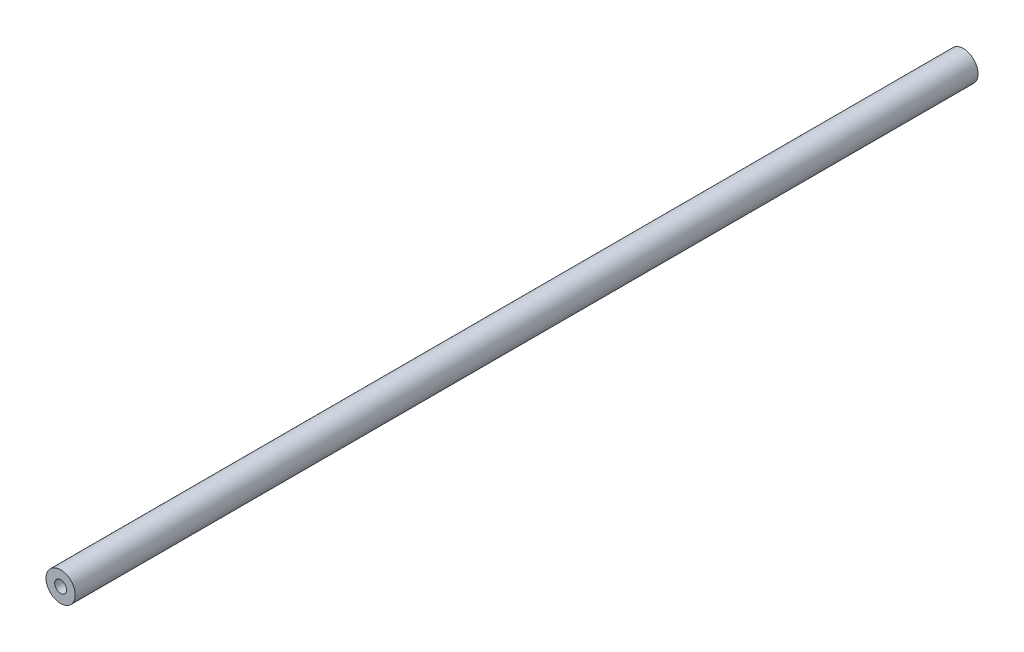
SolidWorks part; units mm, degrees
material "Plain Carbon Steel"
ref_plane "Front Plane" through (0, 0, 0) normal (0, 0, 1) x (1, 0, 0)
ref_plane "Top Plane" through (0, 0, 0) normal (0, 1, 0) x (1, 0, 0)
ref_plane "Right Plane" through (0, 0, 0) normal (1, 0, 0) x (0, 0, -1)
sketch "Sketch1" plane through (0, 0, 0) normal (0, 0, 1) x (1, 0, 0)
  circle A0 centre (0, 0) radius 6.4
  dimension "D1" = 12.8
extrude "Boss-Extrude1" add sketch "Sketch1" along normal blind 395
hole_wizard "#6 (0.204) Diameter Hole1" positions "Sketch2" profile "Sketch3" hole size "#6" standard "ANSI Inch"
sketch "Sketch2" plane through (0, 0, 0) normal (0, 0, -1) x (-1, 0, 0)
  point P0 (0, 0)
sketch "Sketch3" plane through (0, 0, 0) normal (1, 0, 0) x (0, 1, 0)
  line L0 (0, 0) -> (0, 31.5567)
  line L1 (0, 31.5567) -> (2.5908, 30)
  line L2 (2.5908, 30) -> (2.5908, 0)
  line L5 (2.5908, 0) -> (0, 0)
  line L10 (0, 31.5567) -> (-2.5908, 30) construction
  line L11 (0, -6.35) -> (0, 107.95) construction
  dimension "Hole Dia." = 5.1816
  dimension "Hole Depth" = 30
  dimension "Drill Angle" = 118
hole_wizard "#6 (0.204) Diameter Hole2" positions "Sketch4" profile "Sketch5" hole size "#6" standard "ANSI Inch"
sketch "Sketch4" plane through (0, 0, 395) normal (0, 0, 1) x (1, 0, 0)
  point P0 (0, 0)
sketch "Sketch5" plane through (0, 0, 395) normal (1, 0, 0) x (0, -1, 0)
  line L0 (0, 0) -> (0, 31.5567)
  line L1 (0, 31.5567) -> (2.5908, 30)
  line L2 (2.5908, 30) -> (2.5908, 0)
  line L5 (2.5908, 0) -> (0, 0)
  line L10 (0, 31.5567) -> (-2.5908, 30) construction
  line L11 (0, -6.35) -> (0, 107.95) construction
  dimension "Hole Dia." = 5.1816
  dimension "Hole Depth" = 30
  dimension "Drill Angle" = 118
